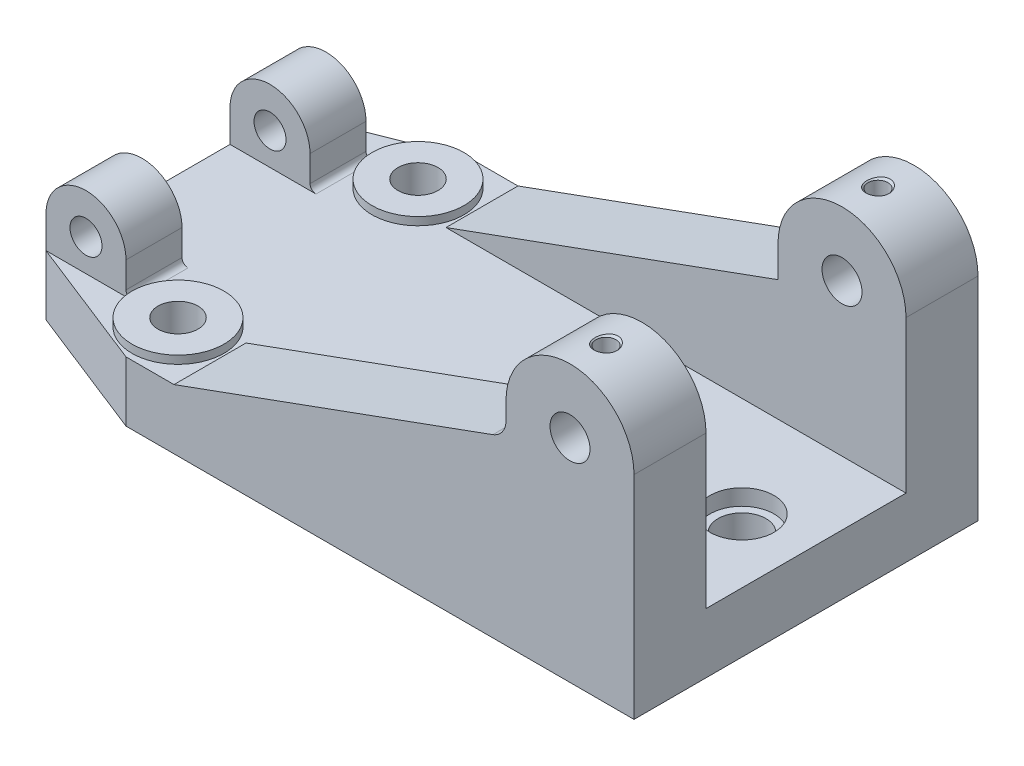
SolidWorks part; units mm, degrees
ref_plane "Front Plane" through (0, 0, 0) normal (0, 0, 1) x (1, 0, 0)
ref_plane "Top Plane" through (0, 0, 0) normal (0, 1, 0) x (1, 0, 0)
ref_plane "Right Plane" through (0, 0, 0) normal (1, 0, 0) x (0, 0, -1)
sketch "Esquisse1" plane through (0, 0, 0) normal (0, 1, 0) x (1, 0, 0)
  line L1 (0, -43) -> (-127, -43)
  line L2 (0, -43) -> (0, 0)
  line L4 (-160, -30) -> (-160, 0)
  line L6 (-160, 0) -> (0, 0)
  line L9 (-160, -30) -> (-127, -43)
  dimension "D1" = 43
  dimension "D2" = 160
  dimension "D3" = 30
extrude "Boss.-Extru.1" add sketch "Esquisse1" along normal blind 15
ref_plane "Plan1" through (0, 0, 43) normal (0, 0, 1) x (1, 0, 0)
sketch "Esquisse2" plane through (0, 0, 43) normal (0, 0, 1) x (1, 0, 0)
  line L0 (-16, 15) -> (-16, 53) construction
  line L1 (-127, 15) -> (0, 15) construction
  line L2 (-32, 45.2095) -> (-32, 53)
  line L3 (0, 15) -> (0, 53)
  line L5 (0, 15) -> (0, 0) construction
  line L6 (-32, 45.2095) -> (-115, 15)
  line L7 (-115, 15) -> (0, 15)
  arc A1 (0, 53) -> (-32, 53) centre (-16, 53) ccw
  point P4 (-16.8903, 29.9865)
  dimension "D4" = 16
  dimension "D1" = 32
  dimension "D2" = 38
  dimension "D3" = 115
  dimension "D5" = 20
extrude "Boss.-Extru.2" add sketch "Esquisse2" against normal blind 18
ref_plane "Plan2" through (0, 0, 30) normal (0, 0, 1) x (1, 0, 0)
sketch "Esquisse3" plane through (0, 0, 30) normal (0, 0, 1) x (1, 0, 0)
  line L0 (-150, 23) -> (-150, 15) construction
  line L4 (-140, 23) -> (-140, 15)
  line L5 (-160, 23) -> (-160, 15)
  line L7 (-160, 15) -> (-160, 0) construction
  line L8 (-160, 15) -> (-127, 15) construction
  line L9 (-160, 15) -> (-140, 15)
  arc A1 (-140, 23) -> (-160, 23) centre (-150, 23) ccw
  point P2 (-150, 23)
  point P9 (0, 0)
  dimension "D1" = 8
  dimension "D2" = 10
extrude "Boss.-Extru.3" add sketch "Esquisse3" against normal blind 14
fillet "Congé1" radius 5 1 edges at (-32, 45.2095, 34)
mirror "Symétrie1" about plane through (0, 0, 0) normal (0, 0, 1) of "Boss.-Extru.3", "Boss.-Extru.2", "Boss.-Extru.1"
sketch "Esquisse4" plane through (0, 0, 30) normal (0, 0, 1) x (1, 0, 0)
  line L0 (-160, 15) -> (-140, 15) construction
  line L1 (-160, 15) -> (-140, 15) construction
  line L2 (-150, 15) -> (-150, 33) construction
  circle A0 centre (-150, 23) radius 4
  arc A1 (-140, 23) -> (-160, 23) centre (-150, 23) ccw construction
  point P4 (0, 0)
  dimension "D2" = 8
  dimension "D1" = 8
extrude "Enlèv. mat.-Extru.1" cut sketch "Esquisse4" against normal through all both and the other way through all
sketch "Esquisse5" plane through (0, 0, 43) normal (0, 0, 1) x (1, 0, 0)
  line L0 (-16, 69) -> (-16, 43.4355) construction
  line L1 (-127, 15) -> (-115, 15) construction
  line L2 (-127, 15) -> (-115, 15) construction
  arc A0 (0, 53) -> (-32, 53) centre (-16, 53) ccw construction
  circle A1 centre (-16, 53) radius 5
  point P8 (0, 0)
  dimension "D1" = 10
  dimension "D2" = 38
extrude "Enlèv. mat.-Extru.2" cut sketch "Esquisse5" against normal through all both
sketch "Esquisse6" plane through (0, 15, 0) normal (0, 1, 0) x (1, 0, 0)
  line L0 (0, 0) -> (-35.6967, 0) construction
  circle A0 centre (-16, 0) radius 5.9876
  point P2 (0, 0)
  dimension "D1" = 11.9753
  dimension "D2" = 16
extrude "Enlèv. mat.-Extru.3" cut sketch "Esquisse6" against normal through all both
sketch "Esquisse7" plane through (0, 15, 0) normal (0, 1, 0) x (1, 0, 0)
  circle A0 centre (-16, 0) radius 8
  circle A1 centre (-16, 0) radius 5.9876 construction
  point P5 (0, 0)
  dimension "D1" = 16
extrude "Enlèv. mat.-Extru.4" cut sketch "Esquisse7" against normal blind 4
ref_plane "Plan4" through (0, 69, 0) normal (0, 1, 0) x (1, 0, 0)
hole_wizard "Trou taraudé M61" positions "Esquisse10" profile "Esquisse11" tap size "M6" standard "ISO" end condition up to next
sketch "Esquisse10" plane through (0, 69, 0) normal (0, 1, 0) x (1, 0, 0)
  line L0 (-115, -25) -> (0, -25) construction
  line L1 (-32, 25) -> (0, 25) construction
  line L2 (-16, 0) -> (-16, -59.3863) construction
  line L3 (-16, 0) -> (-16, 42.1591) construction
  point P0 (-16, 34)
  point P2 (-16, -34)
  point P7 (-16, 25)
  point P20 (0, 0)
  dimension "D1" = 9
  dimension "D2" = 9
sketch "Esquisse11" plane through (-16, 69, -34) normal (1, 0, 0) x (0, 0, 1)
  line L0 (0, 0) -> (0, 11)
  line L1 (0, 11) -> (2.5, 11)
  line L2 (2.5, 11) -> (2.5, 0.525)
  line L3 (2.5, 0.525) -> (3.025, 0)
  line L5 (3.025, 0) -> (0, 0)
  line L6 (-2.5, 0.525) -> (-3.025, 0) construction
  line L11 (0, -6.35) -> (0, 107.95) construction
  dimension "Diamètre du trou pour taraudage jusqu'au prochain" = 5
  dimension "Profondeur du trou pour taraudage jusqu'au prochain" = 11
  dimension "Diamètre du fraisage entrant" = 6.05
  dimension "Angle du fraisage entrant" = 90
sketch "Esquisse12" plane through (0, 15, 0) normal (0, 1, 0) x (1, 0, 0)
  line L0 (-160, -16) -> (-160, -30) construction
  line L1 (-160, 0) -> (-63.3921, 0) construction
  line L2 (-160, 16) -> (-160, -16) construction
  circle A0 centre (-127, -30) radius 5
  circle A1 centre (-127, 30) radius 5
  dimension "D3" = 10
  dimension "D1" = 33
  dimension "D2" = 30
extrude "Enlèv. mat.-Extru.5" cut sketch "Esquisse12" against normal up to next
sketch "Esquisse13" plane through (0, 15, 0) normal (0, 1, 0) x (1, 0, 0)
  circle A0 centre (-127, -30) radius 11.5
  circle A1 centre (-127, 30) radius 11.5
  circle A2 centre (-127, -30) radius 5 construction
  circle A3 centre (-127, -30) radius 5
  circle A4 centre (-127, 30) radius 5 construction
  circle A5 centre (-127, 30) radius 5
  point P10 (0, 0)
  point P11 (0, 0)
  dimension "D1" = 23
  dimension "D2" = 23
extrude "Boss.-Extru.4" add sketch "Esquisse13" along normal blind 2
fillet "Congé2" radius 1.5 2 edges at (-140, 15, 23) (-140, 15, -23)
